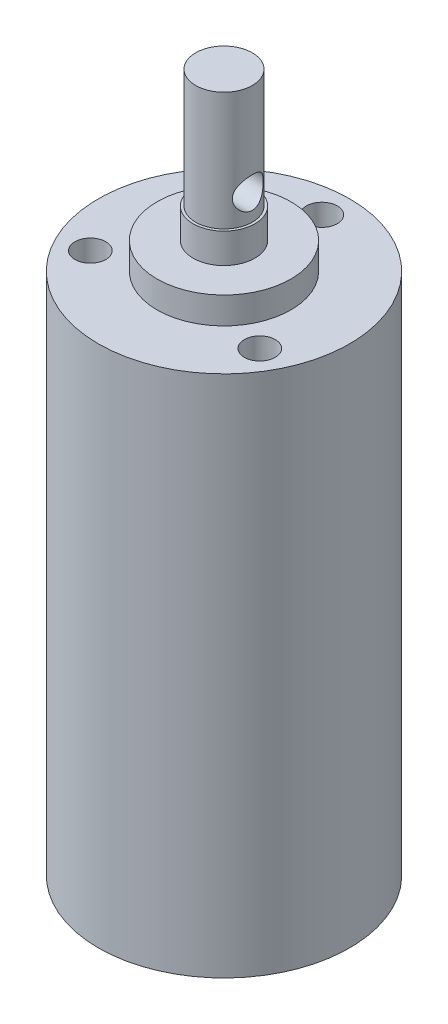
SolidWorks part; units mm, degrees
ref_plane "前视基准面" through (0, 0, 0) normal (0, 0, 1) x (1, 0, 0)
ref_plane "上视基准面" through (0, 0, 0) normal (0, 1, 0) x (1, 0, 0)
ref_plane "右视基准面" through (0, 0, 0) normal (1, 0, 0) x (0, 0, -1)
sketch "草图1" plane through (0, 0, 0) normal (0, 1, 0) x (1, 0, 0)
  circle A0 centre (0, 0) radius 12.2
  dimension "D1" = 24.4
extrude "凸台-拉伸1" add sketch "草图1" along normal blind 50.8
sketch "草图2" plane through (0, 0, 0) normal (0, -1, 0) x (1, 0, 0)
  circle A0 centre (0, 0) radius 2.75
  dimension "D1" = 5.5
extrude "凸台-拉伸2" add sketch "草图2" along normal blind 4
sketch "草图4" plane through (0, 50.8, 0) normal (0, 1, 0) x (1, 0, 0)
  circle A0 centre (0, 0) radius 6.5
  dimension "D1" = 13
extrude "凸台-拉伸3" add sketch "草图4" along normal blind 2.6
sketch "草图5" plane through (0, 53.4, 0) normal (0, 1, 0) x (1, 0, 0)
  circle A0 centre (0, 0) radius 3
  dimension "D1" = 6
extrude "凸台-拉伸4" add sketch "草图5" along normal blind 2.9
sketch "草图6" plane through (0, 56.3, 0) normal (0, 1, 0) x (1, 0, 0)
  circle A0 centre (0, 0) radius 2.75
  dimension "D1" = 5.5
extrude "凸台-拉伸5" add sketch "草图6" along normal blind 11.5
sketch "草图7" plane through (0, 0, 0) normal (1, 0, 0) x (0, 0, -1)
  line L4 (0, 67.8) -> (0, 49.8) construction
  line L5 (2.75, 67.8) -> (-2.75, 67.8) construction
  circle A0 centre (0, 58.8) radius 1.5
  dimension "D1" = 3
  dimension "D2" = 9
extrude "切除-拉伸1" cut sketch "草图7" against normal blind 11.5 and the other way blind 11.5
sketch "草图8" plane through (0, 50.8, 0) normal (0, 1, 0) x (1, 0, 0)
  circle A0 centre (0, 0) radius 9.5 construction
  circle A1 centre (0, 0) radius 12.2
  circle A2 centre (0, 0) radius 12.2 construction
  circle A3 centre (0, 9.5) radius 1.5
  circle A4 centre (8.2272, -4.75) radius 1.5
  circle A5 centre (-8.2272, -4.75) radius 1.5
  point P12 (0, 0)
  dimension "D2" = 19
  dimension "D3" = 3
  dimension "D1" = 0
  dimension "D4" = 3
extrude "切除-拉伸2" cut sketch "草图8" against normal blind 11.5
